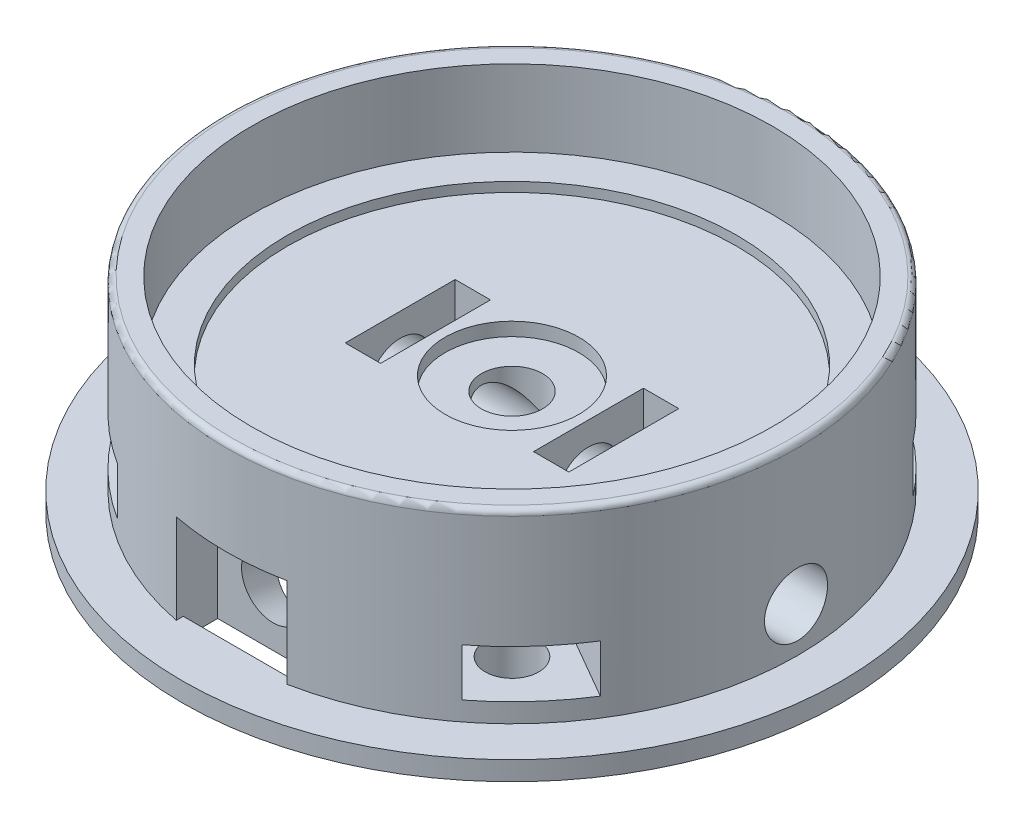
SolidWorks part; units mm, degrees
ref_plane "Front Plane" through (0, 0, 0) normal (0, 0, 1) x (1, 0, 0)
ref_plane "Top Plane" through (0, 0, 0) normal (0, 1, 0) x (1, 0, 0)
ref_plane "Right Plane" through (0, 0, 0) normal (1, 0, 0) x (0, 0, -1)
sketch "Sketch1" plane through (0, 0, 0) normal (0, 1, 0) x (1, 0, 0)
  circle A0 centre (0, 0) radius 14.95
  dimension "D1" = 29.9
extrude "Boss-Extrude1" add sketch "Sketch1" along normal blind 5.7
sketch "Sketch2" plane through (0, 5.7, 0) normal (0, 1, 0) x (1, 0, 0)
  circle A0 centre (0, 0) radius 11.75
  dimension "D1" = 23.5
extrude "Cut-Extrude1" cut sketch "Sketch2" against normal blind 0.5
sketch "Sketch3" plane through (0, 5.7, 0) normal (0, 1, 0) x (1, 0, 0)
  circle A0 centre (0, 0) radius 13.625
  circle A1 centre (0, 0) radius 14.95
  circle A2 centre (0, 0) radius 14.95 construction
  dimension "D1" = 27.25
extrude "Boss-Extrude2" add sketch "Sketch3" along normal blind 4
fillet "Fillet1" radius 0.3 1 edges at (0, 9.7, 14.95)
sketch "Sketch4" plane through (0, 5.2, 0) normal (0, 1, 0) x (1, 0, 0)
  circle A0 centre (0, 0) radius 1.6
  dimension "D1" = 3.2
extrude "Cut-Extrude2" cut sketch "Sketch4" against normal through all
ref_plane "Plane1" through (4, 0, 0) normal (1, 0, 0) x (0, 0, -1)
sketch "Sketch5" plane through (0, 0, 0) normal (1, 0, 0) x (0, 0, -1)
  line L1 (1.6, 5.2) -> (-1.6, 5.2) construction
  line L2 (-2.875, -0.55) -> (2.875, -0.55) construction
  line L3 (-2.875, -0.55) -> (-2.875, 5.2) construction
  line L4 (-2.875, 5.2) -> (2.875, 5.2) construction
  line L5 (2.875, -0.55) -> (2.875, 5.2) construction
  line L6 (-2.875, -0.55) -> (2.875, 5.2) construction
  line L7 (-2.875, 5.2) -> (2.875, -0.55) construction
  circle A0 centre (0, 2.325) radius 1.65
  dimension "D1" = 3.3
  dimension "D2" = 5.75
extrude "Cut-Extrude3" cut sketch "Sketch5" along normal through all
sketch "Sketch6" plane through (0, 0, 0) normal (0, -1, 0) x (1, 0, 0)
  circle A0 centre (0, 0) radius 1.6 construction
  circle A1 centre (0, 0) radius 1.6
  circle A2 centre (0, 0) radius 17.25
  dimension "D1" = 34.5
extrude "Boss-Extrude3" add sketch "Sketch6" along normal blind 1
sketch "Sketch7" plane through (4, 0, 0) normal (1, 0, 0) x (0, 0, -1)
  line L7 (-2.875, 5.2) -> (2.875, 5.2)
  line L8 (-2.875, 5.2) -> (-2.875, -0.55)
  line L9 (-2.875, -0.55) -> (2.875, -0.55)
  line L10 (2.875, 5.2) -> (2.875, -0.55)
  line L11 (-2.875, 5.2) -> (2.875, -0.55) construction
  line L12 (-2.875, -0.55) -> (2.875, 5.2) construction
  point P1 (0, 2.325)
  dimension "D2" = 5.75
extrude "Cut-Extrude4" cut sketch "Sketch7" along normal blind 1.85
ref_axis "Axis1" through (0, 9.4, 0) along (0, -1, 0)
pattern_circular "CirPattern1" count 2 over 360 about axis through (0, 9.4, 0) along (0, -1, 0) of "Cut-Extrude4", "Cut-Extrude3"
ref_plane "Plane2" through (0, 0, 0) normal (0, 0, 1) x (0, -1, 0)
ref_plane "Plane3" through (0, 0, 12.5) normal (0, 0, 1) x (0, -1, 0)
sketch "Sketch11" plane through (0, 0, 12.5) normal (0, 0, 1) x (0, -1, 0)
  line L0 (0, 23.2225) -> (0, -23.2225) construction
  point P4 (0, 0)
ref_plane "Plane4" through (0, 2.5421, 11.9597) normal (0, 0.2079, 0.9781) x (-1, 0, 0)
sketch "Sketch9" plane through (0, 0.4189, 12.411) normal (0, 0.2079, 0.9781) x (0, -0.9781, 0.2079)
  line L0 (-11.3652, 0) -> (-2.1706, 0) construction
  line L2 (1.4283, 2.9) -> (-4.3717, 2.9) construction
  line L3 (1.4283, 2.9) -> (1.4283, -2.9) construction
  line L4 (1.4283, -2.9) -> (-4.3717, -2.9) construction
  line L5 (-4.3717, 2.9) -> (-4.3717, -2.9) construction
  line L6 (1.4283, 2.9) -> (-4.3717, -2.9) construction
  line L7 (1.4283, -2.9) -> (-4.3717, 2.9) construction
  line L8 (0.4283, 23.2225) -> (0.4283, -23.2225) construction
  circle A0 centre (-1.4717, 0) radius 1.65
  dimension "D2" = 3.3
  dimension "D1" = 5.8
  dimension "D3" = 1
extrude "Cut-Extrude5" cut sketch "Sketch9" along normal through all and the other way blind 2
sketch "Sketch10" plane through (0, 0, 12.5) normal (0, 0, 1) x (0, -1, 0)
  line L1 (0.9781, 2.9) -> (-4.6951, 2.9) construction
  line L2 (-4.6951, 2.9) -> (-4.6951, -2.9) construction
  line L3 (0.9781, -2.9) -> (-4.6951, -2.9) construction
  line L5 (0.9781, 2.9) -> (-4.6951, 2.9)
  line L6 (-4.6951, 2.9) -> (-4.6951, -2.9)
  line L7 (0.9781, -2.9) -> (-4.6951, -2.9)
  line L8 (0.9781, 2.9) -> (2.9781, 2.9)
  line L9 (2.9781, 2.9) -> (2.9781, -2.9)
  line L10 (2.9781, -2.9) -> (0.9781, -2.9)
  dimension "D1" = 2
extrude "Cut-Extrude6" cut sketch "Sketch10" along normal blind 1.8
ref_plane "Plane5" through (0, 2.2302, 10.4924) normal (0, 0.2079, 0.9781) x (-1, 0, 0)
sketch "Sketch13" plane through (0, 2.2302, 10.4924) normal (0, 0.2079, 0.9781) x (-1, 0, 0)
  line L0 (-2.4902, -0.2075) -> (-3.8756, 3.5989)
  line L1 (-3.8756, 3.5989) -> (3.8756, 3.5989)
  line L2 (3.8756, 3.5989) -> (2.4902, -0.2075)
  line L3 (0, 0.6989) -> (0, 3.5989) construction
  line L4 (-2.9, 3.5989) -> (2.9, 3.5989) construction
  circle A0 centre (0, 0.6989) radius 1.65 construction
  circle A1 centre (0, 0.6989) radius 1.65 construction
  circle A2 centre (0, 0.6989) radius 2.65 construction
  arc A3 (2.4902, -0.2075) -> (-2.4902, -0.2075) centre (0, 0.6989) cw
  dimension "D1" = 20
  dimension "D2" = 1
ref_plane "Plane6" through (0, 0, 0) normal (-1, 0, 0) x (0, -1, 0)
ref_plane "Plane7" through (0, 0, 14.95) normal (0, 0, 1) x (1, 0, 0)
sketch "Sketch14" plane through (0, 0, 0) normal (-1, 0, 0) x (0, -1, 0)
  line L0 (-3.1606, 10.2947) -> (3.2723, 0) construction
  line L3 (0.0673, 10.9808) -> (-3.1606, 10.2947) construction
  line L5 (-3.1606, 10.2947) -> (-0.9985, 0.1229) construction
  arc A0 (-3.1606, 10.2947) -> (3.2723, 0) centre (14.1981, 13.9844) ccw
  dimension "D1" = 70
sweep "Cut-Sweep1" cut profiles "Sketch13" path "Sketch14"
sketch "Sketch19" plane through (0, 0, 14.95) normal (0, 0, 1) x (1, 0, 0)
  line L0 (2.9, 4.6951) -> (-2.9, 4.6951) construction
  line L1 (2.9, 4.6951) -> (-2.9, 4.6951)
  line L2 (14.95, 0) -> (-14.95, 0) construction
  line L3 (2.9, 0) -> (-2.9, 0)
  line L4 (-2.9, 4.6951) -> (-2.9, 0)
  line L5 (2.9, 4.6951) -> (2.9, 0)
  spline S0 degree 3 poles (-0.1103, 0.7763) (0.2206, 0.7763) (0.4399, 0.8212) (0.8405, 0.99) (1.0254, 1.1159) (1.2535, 1.3495) (1.3227, 1.4364) (1.4409, 1.6192) (1.4907, 1.7158) (1.5713, 1.9192) (1.6018, 2.0256) (1.6413, 2.2393) (1.6508, 2.3478) (1.6481, 2.6782) (1.6047, 2.8939) (1.4812, 3.1989) (1.431, 3.2954) (1.313, 3.4783) (1.2443, 3.5654) (1.0179, 3.8015) (0.8351, 3.9301) (0.4362, 4.1039) (0.2169, 4.1502) (-0.1103, 4.15) (-0.221, 4.1383) (-0.434, 4.0932) (-0.5375, 4.06) (-0.8386, 3.9282) (-1.0184, 3.8015) (-1.2465, 3.5629) (-1.3137, 3.4773) (-1.4313, 3.2948) (-1.4822, 3.1968) (-1.5641, 2.9938) (-1.5952, 2.8896) (-1.6378, 2.6758) (-1.6492, 2.5653) (-1.6515, 2.2381) (-1.6108, 2.0182) (-1.4501, 1.6141) (-1.3285, 1.4262) (-1.1006, 1.193) (-1.0155, 1.1217) (-0.835, 0.9992) (-0.7396, 0.9473) (-0.5381, 0.8627) (-0.4321, 0.8302) (-0.2188, 0.7873) (-0.1103, 0.7763) (0.2206, 0.7763) (0.4399, 0.8212) knots -0.03125 -0.03125 0 0 0.0625 0.0625 0.125 0.125 0.15625 0.15625 0.1875 0.1875 0.21875 0.21875 0.25 0.25 0.3125 0.3125 0.34375 0.34375 0.375 0.375 0.4375 0.4375 0.5 0.5 0.53125 0.53125 0.5625 0.5625 0.625 0.625 0.65625 0.65625 0.6875 0.6875 0.71875 0.71875 0.75 0.75 0.8125 0.8125 0.875 0.875 0.90625 0.90625 0.9375 0.9375 0.96875 0.96875 1 1 1.0625 1.0625 1.125 only from (0, 0.7763) to (0, 0.7763) construction
  spline S1 degree 3 poles (-0.1103, 0.7763) (0.2206, 0.7763) (0.4399, 0.8212) (0.8405, 0.99) (1.0254, 1.1159) (1.2535, 1.3495) (1.3227, 1.4364) (1.4409, 1.6192) (1.4907, 1.7158) (1.5713, 1.9192) (1.6018, 2.0256) (1.6413, 2.2393) (1.6508, 2.3478) (1.6481, 2.6782) (1.6047, 2.8939) (1.4812, 3.1989) (1.431, 3.2954) (1.313, 3.4783) (1.2443, 3.5654) (1.0179, 3.8015) (0.8351, 3.9301) (0.4362, 4.1039) (0.2169, 4.1502) (-0.1103, 4.15) (-0.221, 4.1383) (-0.434, 4.0932) (-0.5375, 4.06) (-0.8386, 3.9282) (-1.0184, 3.8015) (-1.2465, 3.5629) (-1.3137, 3.4773) (-1.4313, 3.2948) (-1.4822, 3.1968) (-1.5641, 2.9938) (-1.5952, 2.8896) (-1.6378, 2.6758) (-1.6492, 2.5653) (-1.6515, 2.2381) (-1.6108, 2.0182) (-1.4501, 1.6141) (-1.3285, 1.4262) (-1.1006, 1.193) (-1.0155, 1.1217) (-0.835, 0.9992) (-0.7396, 0.9473) (-0.5381, 0.8627) (-0.4321, 0.8302) (-0.2188, 0.7873) (-0.1103, 0.7763) (0.2206, 0.7763) (0.4399, 0.8212) knots -0.03125 -0.03125 0 0 0.0625 0.0625 0.125 0.125 0.15625 0.15625 0.1875 0.1875 0.21875 0.21875 0.25 0.25 0.3125 0.3125 0.34375 0.34375 0.375 0.375 0.4375 0.4375 0.5 0.5 0.53125 0.53125 0.5625 0.5625 0.625 0.625 0.65625 0.65625 0.6875 0.6875 0.71875 0.71875 0.75 0.75 0.8125 0.8125 0.875 0.875 0.90625 0.90625 0.9375 0.9375 0.96875 0.96875 1 1 1.0625 1.0625 1.125 only from (0, 0.7763) to (0, 0.7763) construction
extrude "Cut-Extrude11" cut sketch "Sketch19" against normal up to surface (0.65 mm away) up to face at (0, 1.8476, 14.3)
pattern_circular "CirPattern2" count 2 over 360 about axis through (0, 9.4, 0) along (0, -1, 0) of "Cut-Extrude5", "Cut-Sweep1", "Cut-Extrude6", "Cut-Extrude11"
sketch "Sketch16" plane through (0, -1, 0) normal (0, -1, 0) x (1, 0, 0)
  line L0 (0, 0) -> (-12.1976, 12.1976) construction
  line L1 (0, 11.1539) -> (0, -11.1539) construction
  circle A0 centre (0, 0) radius 17.25 construction
  circle A1 centre (-8.5206, 8.5206) radius 1.4
  circle A2 centre (-8.5206, 8.5206) radius 2.9 construction
  circle A3 centre (0, 0) radius 14.95 construction
  dimension "D2" = 2.8
  dimension "D3" = 5.8
  dimension "D1" = 45
extrude "Cut-Extrude8" cut sketch "Sketch16" against normal blind 4.5
sketch "Sketch17" plane through (0, 3.5, 0) normal (0, -1, 0) x (1, 0, 0)
  line L0 (0, 11.1539) -> (0, -11.1539) construction
  line L1 (-9.964, 11.0206) -> (-11.4074, 8.5206) construction
  line L2 (-11.4074, 8.5206) -> (-9.964, 6.0206)
  line L3 (-9.964, 6.0206) -> (-7.0773, 6.0206)
  line L4 (-7.0773, 6.0206) -> (-5.6339, 8.5206)
  line L5 (-5.6339, 8.5206) -> (-7.0773, 11.0206)
  line L6 (-7.0773, 11.0206) -> (-9.964, 11.0206) construction
  line L7 (-7.0773, 11.0206) -> (-8.0109, 12.6377)
  line L8 (-8.0109, 12.6377) -> (-12.341, 10.1377)
  line L9 (-12.341, 10.1377) -> (-11.4074, 8.5206)
  circle A0 centre (-8.5206, 8.5206) radius 2.5 construction
  circle A1 centre (0, 0) radius 14.95 construction
  dimension "D1" = 5
  dimension "D2" = 30
extrude "Cut-Extrude9" cut sketch "Sketch17" along normal blind 2.5
pattern_circular "CirPattern3" count 4 over 360 about axis through (0, 9.4, 0) along (0, -1, 0) of "Cut-Extrude8", "Cut-Extrude9"
sketch "Sketch18" plane through (0, 5.2, 0) normal (0, 1, 0) x (1, 0, 0)
  circle A2 centre (0, 0) radius 3.5
  dimension "D1" = 7
extrude "Cut-Extrude10" cut sketch "Sketch18" against normal blind 0.7
